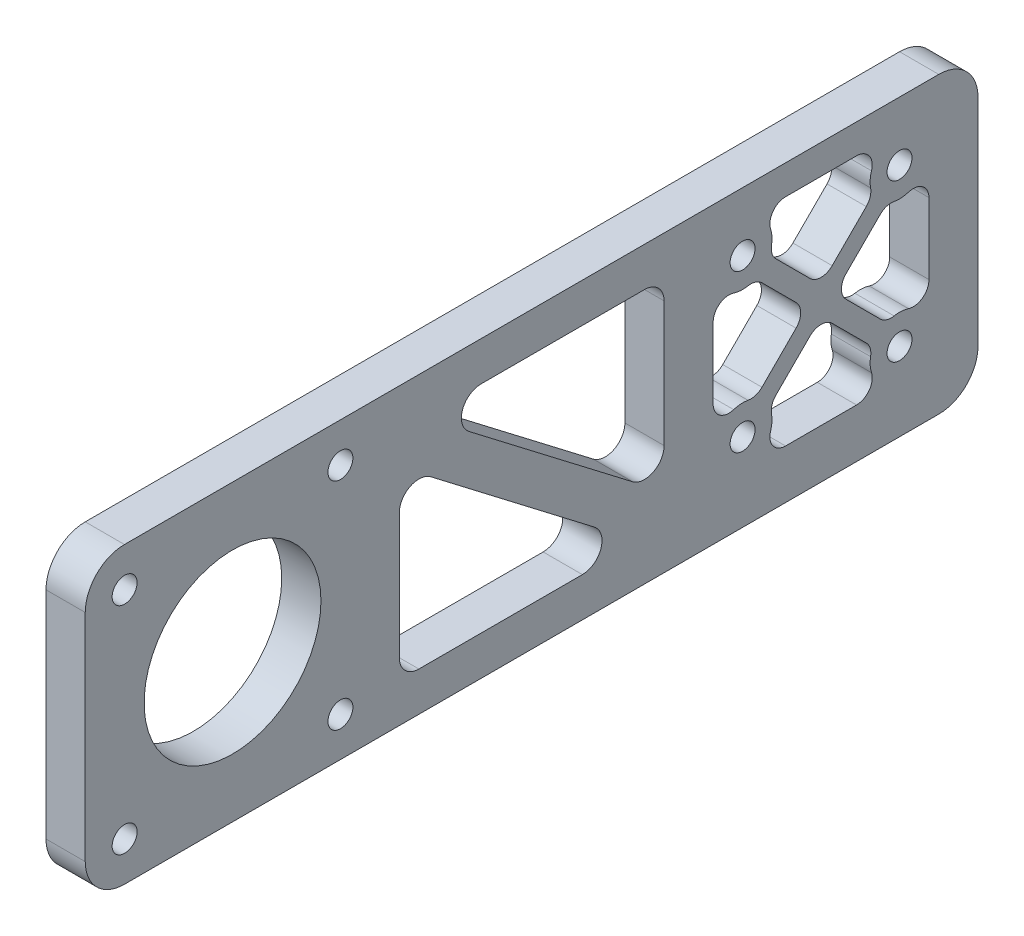
SolidWorks part; units mm, degrees
material "6061-T6 (SS)"
ref_plane "Front" through (0, 0, 0) normal (0, 0, 1) x (1, 0, 0)
ref_plane "Top" through (0, 0, 0) normal (0, 1, 0) x (1, 0, 0)
ref_plane "Right" through (0, 0, 0) normal (1, 0, 0) x (0, 0, -1)
sketch "Sketch1" plane through (0, 0, 0) normal (1, 0, 0) x (0, 0, -1)
  line L0 (0, -23.8125) -> (0, 23.8125)
  line L3 (0, 23.8125) -> (-144.4879, 23.8125)
  line L4 (-144.4879, -23.8125) -> (0, -23.8125)
  line L5 (-144.4879, 23.8125) -> (-144.4879, -23.8125)
  line L6 (-120.65, 23.8125) -> (-120.65, -23.8125) construction
  circle A1 centre (-120.65, 0) radius 14.3129
  point P4 (0, 0)
  dimension "D3" = 28.6258
  dimension "D1" = 9.525
  dimension "D2" = 47.625
  dimension "D5" = 120.65
extrude "Boss-Extrude1" add sketch "Sketch1" along normal blind 6.35
fillet "Fillet1" radius 6.35 4 edges at (3.175, -23.8125, 144.4879) (3.175, 23.8125, 144.4879) (3.175, -23.8125, 0) (3.175, 23.8125, 0)
sketch "Sketch4" plane through (0, 0, 0) normal (-1, 0, 0) x (0, 0, 1)
  point P0 (103.1875, 17.4625)
  point P3 (138.1125, 17.4625)
  point P6 (138.1125, -17.4625)
  point P9 (103.1875, -17.4625)
hole_wizard "#10-32 Tapped Hole1" positions "Sketch4" profile "Sketch3" tap size "#10-32" standard "ANSI Inch" end condition up to next
sketch "Sketch3" plane through (0, 17.4625, 103.1875) normal (0, 1, 0) x (0, 0, 1)
  line L0 (0, 0) -> (0, 6.35)
  line L1 (0, 6.35) -> (2.0193, 6.35)
  line L2 (2.0193, 6.35) -> (2.0193, 0)
  line L5 (2.0193, 0) -> (0, 0)
  line L11 (0, -6.35) -> (0, 107.95) construction
  dimension "Thru Tap Drill Dia." = 4.0386
  dimension "Thru Tap Drill Depth" = 6.35
cosmetic thread "Hole Thread1" parameters "D2"=4.826
cosmetic thread "Hole Thread2" parameters "D2"=4.826
cosmetic thread "Hole Thread3" parameters "D2"=4.826
cosmetic thread "Hole Thread4" parameters "D2"=4.826
sketch "Sketch7" plane through (6.35, 0, 0) normal (1, 0, 0) x (0, 0, -1)
  line L0 (-50.8, 23.8125) -> (-50.8, -23.8125) construction
  line L1 (-6.35, 23.8125) -> (-138.1379, 23.8125) construction
  line L2 (-138.1379, -23.8125) -> (-6.35, -23.8125) construction
  line L4 (0, -17.4625) -> (0, 17.4625) construction
  line L5 (-50.8, -23.8125) -> (-38.1, -11.1125) construction
  line L8 (-12.7, -11.1125) -> (0, -23.8125) construction
  line L9 (0, -17.4625) -> (0, 17.4625) construction
  line L10 (-138.1379, -23.8125) -> (-6.35, -23.8125) construction
  point P0 (-12.7, 14.2875)
  point P2 (-38.1, 14.2875)
  point P4 (-38.1, -11.1125)
  point P6 (-12.7, -11.1125)
  point P32 (0, 0)
  dimension "D1" = 50.8
  dimension "D2" = 25.4
  dimension "D3" = 25.4
  dimension "D4" = 12.7
hole_wizard "#10-32 Tapped Hole2" positions "Sketch7" profile "Sketch6" tap size "#10-32" standard "ANSI Inch" end condition up to next
sketch "Sketch6" plane through (6.35, 14.2875, 12.7) normal (0, 1, 0) x (0, 0, -1)
  line L0 (0, 0) -> (0, 6.35)
  line L1 (0, 6.35) -> (2.0193, 6.35)
  line L2 (2.0193, 6.35) -> (2.0193, 0)
  line L5 (2.0193, 0) -> (0, 0)
  line L11 (0, -6.35) -> (0, 107.95) construction
  dimension "Thru Tap Drill Dia." = 4.0386
  dimension "Thru Tap Drill Depth" = 6.35
sketch "Sketch8" plane through (6.35, 0, 0) normal (1, 0, 0) x (0, 0, -1)
  line L0 (-80.4367, 17.4625) -> (-53.975, 17.4625)
  line L1 (-93.6625, 5.9893) -> (-93.6625, -14.2875)
  line L3 (-90.4875, -17.4625) -> (-64.0258, -17.4625)
  line L4 (-50.8, -5.9893) -> (-50.8, 14.2875)
  line L6 (-6.35, 23.8125) -> (-138.1379, 23.8125) construction
  line L7 (-138.1379, -23.8125) -> (-6.35, -23.8125) construction
  line L8 (0, -17.4625) -> (0, 17.4625) construction
  line L9 (-82.3679, 11.7673) -> (-55.9061, -8.5095)
  line L10 (-62.0946, -11.7673) -> (-88.5564, 8.5095)
  line L11 (-93.6625, 12.4221) -> (-89.8002, 17.4625) construction
  line L12 (-38.1, 19.05) -> (-12.7, 19.05)
  line L13 (-7.9375, 14.2875) -> (-7.9375, -11.1125)
  line L14 (-38.1, -15.875) -> (-12.7, -15.875)
  line L15 (-42.8625, 14.2875) -> (-42.8625, -11.1125)
  line L16 (-33.8025, 12.235) -> (-25.4, 3.8326)
  line L17 (-16.9975, -9.06) -> (-25.4, -0.6576)
  line L18 (-16.9975, 12.235) -> (-25.4, 3.8326)
  line L19 (-14.7525, 9.99) -> (-23.1549, 1.5875)
  line L20 (-23.1549, 1.5875) -> (-14.7525, -6.815)
  line L21 (-27.6451, 1.5875) -> (-36.0475, 9.99)
  line L22 (-27.6451, 1.5875) -> (-36.0475, -6.815)
  line L23 (-25.4, -0.6576) -> (-33.8025, -9.06)
  circle A0 centre (-103.1875, 17.4625) radius 2.0193 construction
  arc A1 (-88.5564, 8.5095) -> (-93.6625, 5.9893) centre (-90.4875, 5.9893) ccw
  arc A2 (-93.6625, -14.2875) -> (-90.4875, -17.4625) centre (-90.4875, -14.2875) ccw
  arc A3 (-62.0946, -11.7673) -> (-64.0258, -17.4625) centre (-64.0258, -14.2875) cw
  arc A4 (-55.9061, -8.5095) -> (-50.8, -5.9893) centre (-53.975, -5.9893) ccw
  arc A5 (-53.975, 17.4625) -> (-50.8, 14.2875) centre (-53.975, 14.2875) cw
  arc A6 (-82.3679, 11.7673) -> (-80.4367, 17.4625) centre (-80.4367, 14.2875) cw
  arc A7 (-33.8025, 12.235) -> (-38.1, 19.05) centre (-38.1, 14.2875) ccw
  arc A8 (-14.7525, 9.99) -> (-7.9375, 14.2875) centre (-12.7, 14.2875) ccw
  arc A9 (-16.9975, -9.06) -> (-12.7, -15.875) centre (-12.7, -11.1125) ccw
  arc A10 (-36.0475, -6.815) -> (-42.8625, -11.1125) centre (-38.1, -11.1125) ccw
  arc A11 (-7.9375, -11.1125) -> (-14.7525, -6.815) centre (-12.7, -11.1125) ccw
  arc A12 (-42.8625, 14.2875) -> (-36.0475, 9.99) centre (-38.1, 14.2875) ccw
  arc A13 (-12.7, 19.05) -> (-16.9975, 12.235) centre (-12.7, 14.2875) ccw
  arc A14 (-38.1, -15.875) -> (-33.8025, -9.06) centre (-38.1, -11.1125) ccw
  point P29 (0, 0)
  point P35 (-23.5271, 1.9038)
  point P38 (-38.1, 19.05)
  dimension "D6" = 3.175
  dimension "D7" = 9.525
  dimension "D1" = 6.35
  dimension "D2" = 6.35
  dimension "D3" = 50.8
  dimension "D4" = 9.525
  dimension "D5" = 6.35
  dimension "D9" = 3.175
  dimension "D10" = 3.175
extrude "Cut-Extrude1" cut sketch "Sketch8" against normal through all
fillet "Fillet2" radius 2.54 20 edges at (3.175, 1.5875, 27.6451) (3.175, -6.815, 36.0475) (3.175, -11.1125, 42.8625) (3.175, 14.2875, 42.8625) (3.175, 12.235, 33.8025) (3.175, 19.05, 38.1) (3.175, 19.05, 12.7) (3.175, 12.235, 16.9975) (3.175, 3.8326, 25.4) (3.175, -0.6576, 25.4) (3.175, -9.06, 16.9975) (3.175, -15.875, 12.7) (3.175, -15.875, 38.1) (3.175, -9.06, 33.8025) (3.175, -11.1125, 7.9375) (3.175, -6.815, 14.7525) (3.175, 1.5875, 23.1549) (3.175, 9.99, 14.7525) (3.175, 14.2875, 7.9375) (3.175, 9.99, 36.0475)
